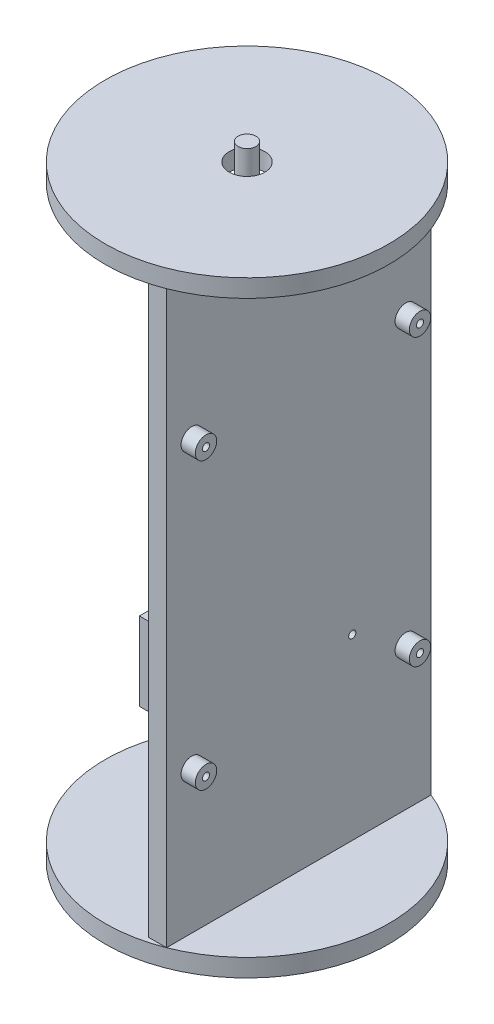
SolidWorks part; units mm, degrees
ref_plane "Front Plane" through (0, 0, 0) normal (0, 0, 1) x (1, 0, 0)
ref_plane "Top Plane" through (0, 0, 0) normal (0, 1, 0) x (1, 0, 0)
ref_plane "Right Plane" through (0, 0, 0) normal (1, 0, 0) x (0, 0, -1)
sketch "Sketch1" plane through (0, 0, 0) normal (0, 1, 0) x (1, 0, 0)
  circle A0 centre (0, 0) radius 50.546
  dimension "D1" = 101.092
extrude "Boss-Extrude1" add sketch "Sketch1" along normal blind 6.35
sketch "Sketch3" plane through (0, 6.35, 0) normal (0, 1, 0) x (1, 0, 0)
  line L0 (-50.546, 0) -> (50.546, 0) construction
  line L1 (0, -50.546) -> (0, 50.546) construction
  line L2 (15.24, -48.1938) -> (15.24, 48.1938) construction
  line L8 (12.065, -47.0721) -> (18.415, -47.0721)
  line L9 (12.065, -47.0721) -> (12.065, 47.0721)
  line L14 (12.065, 47.0721) -> (18.415, 47.0721)
  line L15 (18.415, -47.0721) -> (18.415, 47.0721)
  line L16 (12.065, -47.0721) -> (18.415, 47.0721) construction
  line L17 (12.065, 47.0721) -> (18.415, -47.0721) construction
  circle A0 centre (0, 0) radius 50.546 construction
  point P0 (15.24, 0)
  point P7 (0, 0)
  point P11 (0, 0)
  dimension "D1" = 15.24
  dimension "D2" = 6.35
extrude "Boss-Extrude2" add sketch "Sketch3" along normal blind 203.2
sketch "Sketch4" plane through (0, 209.55, 0) normal (0, 1, 0) x (1, 0, 0)
  arc A0 (18.415, 47.0721) -> (18.415, -47.0721) centre (0, 0) ccw construction
  arc A1 (18.415, -47.0721) -> (18.415, 47.0721) centre (0, 0) ccw construction
  arc A2 (18.415, 47.0721) -> (18.415, -47.0721) centre (0, 0) ccw
  arc A3 (18.415, -47.0721) -> (18.415, 47.0721) centre (0, 0) ccw
extrude "Boss-Extrude3" add sketch "Sketch4" along normal blind 6.35
sketch "Sketch5" plane through (0, 215.9, 0) normal (0, 1, 0) x (1, 0, 0)
  circle A0 centre (0, 0) radius 6.35
  dimension "D1" = 12.7
extrude "Cut-Extrude1" cut sketch "Sketch5" against normal up to next
sketch "Sketch7" plane through (0, 6.35, 0) normal (0, 1, 0) x (1, 0, 0)
  circle A0 centre (0, 0) radius 3.175
  dimension "D1" = 6.35
extrude "Boss-Extrude4" add sketch "Sketch7" along normal blind 215.9
sketch "Sketch8" plane through (12.065, 0, 0) normal (-1, 0, 0) x (0, 0, 1)
  line L0 (-19.05, 6.35) -> (-19.05, 209.55) construction
  line L1 (-47.0721, 6.35) -> (47.0721, 6.35) construction
  line L2 (-50.546, 209.55) -> (50.546, 209.55) construction
  circle A0 centre (-19.05, 69.85) radius 1.27
  dimension "D3" = 2.54
  dimension "D1" = 19.05
  dimension "D2" = 63.5
extrude "Cut-Extrude2" cut sketch "Sketch8" against normal through all
ref_axis "Axis1" through (0, 222.25, 0) along (0, -1, 0)
sketch "Sketch9" plane through (12.065, 0, 0) normal (-1, 0, 0) x (0, 0, 1)
  line L0 (-47.0721, 209.55) -> (-47.0721, 6.35) construction
  line L1 (-47.0721, 107.95) -> (-43.8971, 107.95)
  line L2 (-47.0721, 107.95) -> (-47.0721, 31.75)
  line L3 (-47.0721, 31.75) -> (-43.8971, 31.75)
  line L4 (-43.8971, 107.95) -> (-43.8971, 31.75)
  line L5 (-47.0721, 6.35) -> (47.0721, 6.35) construction
  dimension "D1" = 3.175
  dimension "D2" = 25.4
extrude "Boss-Extrude5" add sketch "Sketch9" along normal blind 19.05
sketch "Sketch10" plane through (0, 0, -43.8971) normal (0, 0, 1) x (1, 0, 0)
  line L0 (12.065, 209.55) -> (12.065, 6.35) construction
  line L1 (-6.985, 31.75) -> (12.065, 31.75)
  line L2 (-6.985, 31.75) -> (-6.985, 34.29)
  line L3 (-6.985, 34.29) -> (12.065, 34.29)
  line L4 (12.065, 31.75) -> (12.065, 34.29)
  dimension "D1" = 2.54
extrude "Boss-Extrude6" add sketch "Sketch10" along normal blind 25.4
sketch "Sketch11" plane through (0, 34.29, 0) normal (0, 1, 0) x (1, 0, 0)
  line L0 (-6.985, 36.3127) -> (12.065, 36.3127) construction
  line L1 (-6.985, 18.4971) -> (-6.985, 43.8971) construction
  line L3 (12.065, 18.4971) -> (12.065, 43.8971) construction
  circle A0 centre (-1.905, 36.3127) radius 1.27
  dimension "D1" = 2.54
  dimension "D2" = 5.08
extrude "Cut-Extrude3" cut sketch "Sketch11" against normal up to next
sketch "Sketch12" plane through (12.065, 0, 0) normal (-1, 0, 0) x (0, 0, 1)
  line L0 (17.1526, 82.3158) -> (17.1526, 85.7887) construction
  line L1 (17.1526, 86.2887) -> (29.5526, 86.2887)
  line L2 (17.1526, 86.2887) -> (17.1526, 63.4887)
  line L3 (17.1526, 63.4887) -> (29.5526, 63.4887)
  line L4 (29.5526, 86.2887) -> (29.5526, 63.4887)
  line L5 (27.7778, 86.2887) -> (18.9275, 86.2887) construction
  line L6 (29.5526, 65.2635) -> (29.5526, 84.5139) construction
  line L7 (18.9275, 63.4887) -> (27.7778, 63.4887) construction
  line L9 (14.6126, 60.9487) -> (32.0926, 60.9487)
  line L10 (32.0926, 88.8287) -> (32.0926, 60.9487)
  line L11 (14.6126, 88.8287) -> (32.0926, 88.8287)
  line L12 (14.6126, 88.8287) -> (14.6126, 60.9487)
  dimension "D1" = 2.54
extrude "Boss-Extrude7" add sketch "Sketch12" along normal up to surface (18.3 mm away)
sketch "Sketch13" plane through (18.415, 0, 0) normal (1, 0, 0) x (0, 0, -1)
  line L0 (-47.0721, 209.55) -> (47.0721, 6.35) construction
  line L2 (-38.1, 57.15) -> (38.1, 57.15) construction
  line L3 (-38.1, 57.15) -> (-38.1, 158.75) construction
  line L4 (-38.1, 158.75) -> (38.1, 158.75) construction
  line L5 (38.1, 57.15) -> (38.1, 158.75) construction
  line L6 (-38.1, 57.15) -> (38.1, 158.75) construction
  line L7 (-38.1, 158.75) -> (38.1, 57.15) construction
  circle A0 centre (38.1, 158.75) radius 1.27
  circle A1 centre (-38.1, 158.75) radius 1.27
  circle A2 centre (-38.1, 57.15) radius 1.27
  circle A3 centre (38.1, 57.15) radius 1.27
  circle A4 centre (-38.1, 158.75) radius 3.81
  circle A5 centre (38.1, 158.75) radius 3.81
  circle A6 centre (-38.1, 57.15) radius 3.81
  circle A7 centre (38.1, 57.15) radius 3.81
  point P4 (0, 107.95)
  dimension "D1" = 2.54
  dimension "D3" = 76.2
  dimension "D4" = 101.6
  dimension "D2" = 2.54
extrude "Boss-Extrude8" add sketch "Sketch13" along normal blind 5.08
